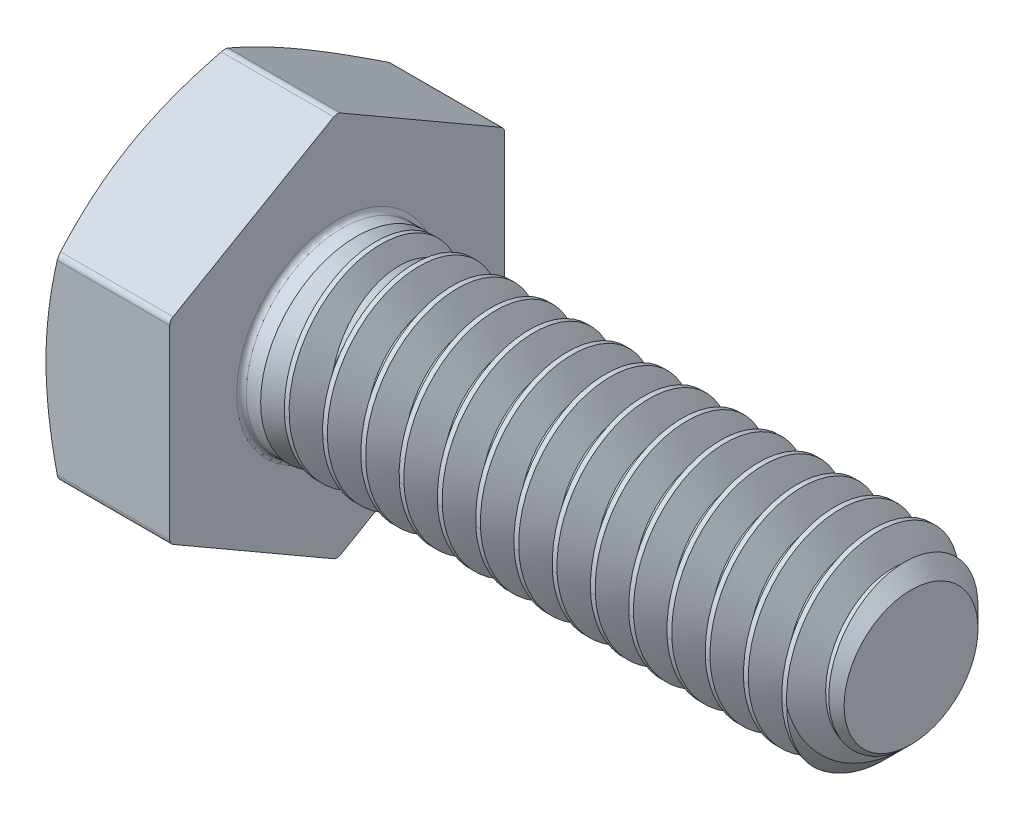
SolidWorks part; units mm, degrees
ref_plane "Front Plane" through (0, 0, 0) normal (0, 0, 1) x (1, 0, 0)
ref_plane "Top Plane" through (0, 0, 0) normal (0, 1, 0) x (1, 0, 0)
ref_plane "Right Plane" through (0, 0, 0) normal (1, 0, 0) x (0, 0, -1)
sketch "Sketch1" plane through (0, 0, 0) normal (0, 0, 1) x (1, 0, 0)
  line L0 (0, 0) -> (19.05, 0) construction
  line L1 (0, 0) -> (-4.3656, 0) construction
  line L2 (0, 5.5562) -> (0, -5.5562) construction
  line L3 (-4.3656, 5.5562) -> (-4.3656, -5.5563) construction
  line L4 (19.05, 3.175) -> (19.05, -3.175) construction
  line L8 (17.78, 3.175) -> (19.05, 3.175) construction
  point P8 (17.78, 0)
  point P11 (14.605, -3.175)
  point P12 (0.635, 0)
  dimension "Head Height" = 4.3656
  dimension "Head Width" = 11.1125
  dimension "Length" = 19.05
  dimension "Thread Size" = 6.35
  dimension "D1" = 4.445
  dimension "Thread Pitch" = 1.27
  dimension "D2" = 0.635
sketch "Sketch2" plane through (0, 0, 0) normal (1, 0, 0) x (0, 0, -1)
  circle A0 centre (0, 0) radius 3.175
extrude "Boss-Extrude1" add sketch "Sketch2" along normal up to vertex (19.05 mm away) up to point (19.05, 3.175, 0)
sketch "Sketch3" plane through (0, 0, 0) normal (-1, 0, 0) x (0, 0, 1)
  line L0 (0, 6.4158) -> (0, 0) construction
  line L1 (0, 6.4158) -> (-5.5563, 3.2079)
  line L2 (-5.5563, 3.2079) -> (-5.5562, -3.2079)
  line L3 (-5.5562, -3.2079) -> (0, -6.4158)
  line L4 (0, -6.4158) -> (5.5563, -3.2079)
  line L5 (5.5563, -3.2079) -> (5.5563, 3.2079)
  line L6 (5.5563, 3.2079) -> (0, 6.4158)
  circle A0 centre (0, 0) radius 5.5562 construction
extrude "Boss-Extrude2" add sketch "Sketch3" along normal up to vertex (4.3656 mm away) up to point (-4.3656, 5.5562, 0)
sketch "Sketch5" plane through (-4.3656, 0, 0) normal (-1, 0, 0) x (0, 0, 1)
  circle A0 centre (0, 0) radius 5.5562 construction
  circle A1 centre (0, 0) radius 5.5562 construction
  circle A2 centre (0, 0) radius 5.0006
  dimension "D1" = 0.5556
extrude "Cut-Extrude1" cut sketch "Sketch5" against normal up to vertex (4.3656 mm away) draft 65 flip side to cut up to point (0, 0, 0)
fillet "Fillet7" radius 0.2223 6 edges at (-1.8529, -6.4158, 0) (-1.8529, -3.2079, -5.5562) (-1.8529, 3.2079, -5.5563) (-1.8529, 6.4158, 0) (-1.8529, -3.2079, 5.5563) (-1.8529, 3.2079, 5.5563)
chamfer "Chamfer1" distance 0.9525 angle 45 1 edges at (19.05, 0, -3.175)
fillet "Fillet4" radius 0.1588 1 edges at (0, 0, 3.175)
sketch "Reference Sketch1" plane through (0, 0, 0) normal (1, 0, 0) x (0, 0, -1)
  line L1 (0, 6.4158) -> (-5.5562, 3.2079)
  line L2 (-5.5562, 3.2079) -> (-5.5562, -3.2079)
  line L3 (-5.5562, -3.2079) -> (0, -6.4158)
  line L4 (0, -6.4158) -> (5.5562, -3.2079)
  line L5 (5.5562, -3.2079) -> (5.5562, 3.2079)
  line L6 (5.5562, 3.2079) -> (0, 6.4158)
  circle A0 centre (0, 0) radius 5.5562 construction
  circle A1 centre (0, 0) radius 5.5562
sketch "Sketch12" plane through (19.05, 0, 0) normal (1, 0, 0) x (0, 0, -1)
  circle A1 centre (0, 0) radius 3.175
ref_plane "Plane2" through (0.635, 0, 0) normal (1, 0, 0) x (0, 0, -1)
split "Split1" trim tools "Plane2" bodies to split 105 116 resulting bodies 118 119
curve "Helix/Spiral2" pitch 1.27 height 21.59 radius 3.175 centre (19.05, 0, 0) axis (-1, 0, 0) start towards (0, 1, 0) parameters "Pitch"=1.27
sketch "Sketch13" plane through (0, 0, 0) normal (0, 0, 1) x (1, 0, 0)
  line L0 (18.9706, 3.3125) -> (19.6056, 2.2126) construction
  line L1 (19.6056, 2.2126) -> (20.2406, 3.3125) construction
  line L2 (20.2406, 3.3125) -> (18.9706, 3.3125) construction
  line L3 (19.6056, 2.2126) -> (19.6056, 2.3501) construction
  line L4 (19.05, 3.175) -> (20.1613, 3.175) construction
  line L5 (19.6056, 3.175) -> (19.6056, 3.3125) construction
  line L6 (19.685, 2.3501) -> (20.2009, 3.2437)
  line L7 (19.685, 2.3501) -> (19.5263, 2.3501)
  line L8 (20.2009, 3.2437) -> (19.0103, 3.2437)
  line L9 (17.78, 3.175) -> (19.05, 3.175) construction
  line L10 (19.0103, 3.2437) -> (19.5263, 2.3501)
  point P15 (19.6056, 3.2437)
  dimension "D1" = 0.1588
sweep "Cut-Sweep1" cut profiles "Sketch13" path "Helix/Spiral2" align with end faces yes
sketch "Sketch14" plane through (0.635, 0, 0) normal (1, 0, 0) x (0, 0, -1)
  circle A1 centre (0, 0) radius 3.175
  circle A2 centre (0, 0) radius 3.175
  dimension "D1" = 0
extrude "Boss-Extrude4" add sketch "Sketch14" along normal through all draft 31.8
equation "\"D3@Helix/Spiral2\"=\"Length@Sketch1\" + \"Thread Pitch@Sketch1\"*2"
equation "\"D1@Chamfer1\"=\"Thread Pitch@Sketch1\"*0.750"
equation "\"D1@Sketch1\"=\"Thread Pitch@Sketch1\"*3.5"
equation "\"Pitch@Helix/Spiral2\"=\"Thread Pitch@Sketch1\""
equation "\"D1@Sketch13\"=\"Thread Pitch@Sketch1\"*0.125"
equation "\"D1@Sketch5\"=\"Head Width@Sketch1\"*0.05"
equation "\"D1@Fillet4\"=\"Thread Size@Sketch1\"*0.025"
equation "\"D2@Sketch1\"=\"Thread Pitch@Sketch1\"*0.5"
equation "\"D1@Fillet7\"=\"Head Width@Sketch1\"*0.02"
